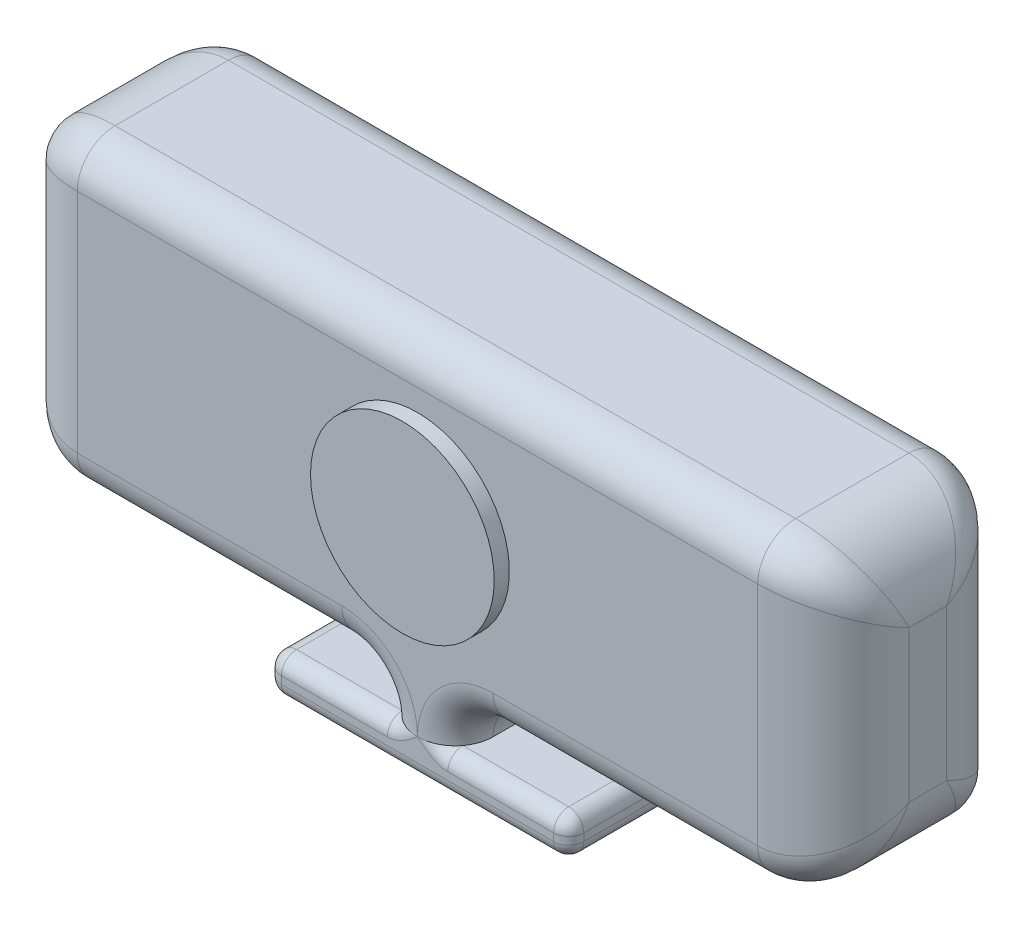
SolidWorks part; units mm, degrees
ref_plane "Front Plane" through (0, 0, 0) normal (0, 0, 1) x (1, 0, 0)
ref_plane "Top Plane" through (0, 0, 0) normal (0, 1, 0) x (1, 0, 0)
ref_plane "Right Plane" through (0, 0, 0) normal (1, 0, 0) x (0, 0, -1)
sketch "Sketch1" plane through (0, 0, 0) normal (0, 0, 1) x (1, 0, 0)
  line L0 (-55, -20) -> (-5, -20)
  line L1 (-55, 20) -> (55, 20)
  line L2 (-55, 20) -> (-55, -20)
  line L4 (55, 20) -> (55, -20)
  line L5 (-55, 20) -> (55, -20) construction
  line L6 (-55, -20) -> (55, 20) construction
  line L7 (-5, -20) -> (-5, -25)
  line L8 (-5, -25) -> (-20, -25)
  line L9 (-20, -25) -> (-20, -30)
  line L10 (-20, -30) -> (20, -30)
  line L11 (20, -30) -> (20, -25)
  line L12 (20, -25) -> (5, -25)
  line L13 (5, -25) -> (5, -20)
  line L14 (5, -20) -> (55, -20)
  point P0 (0, 0)
  dimension "D1" = 110
  dimension "D2" = 40
  dimension "D3" = 10
  dimension "D4" = 5
  dimension "D5" = 40
  dimension "D6" = 5
extrude "Boss-Extrude1" add sketch "Sketch1" against normal blind 25
sketch "Sketch2" plane through (0, 0, 0) normal (0, 0, 1) x (1, 0, 0)
  circle A0 centre (0, 0) radius 12.1512
extrude "Boss-Extrude2" add sketch "Sketch2" along normal blind 2
fillet "Fillet1" radius 10 8 edges at (-55, -20, -12.5) (-55, 0, -25) (-55, 20, -12.5) (-55, 0, 0) (55, 20, -12.5) (55, 0, -25) (55, -20, -12.5) (55, 0, 0)
fillet "Fillet2" radius 5 16 edges at (-52.0711, -17.0711, -22.0711) (-52.0711, -17.0711, -2.9289) (52.0711, -17.0711, -2.9289) (52.0711, -17.0711, -22.0711) (52.0711, 17.0711, -2.9289) (-52.0711, 17.0711, -2.9289) (52.0711, 17.0711, -22.0711) (-52.0711, 17.0711, -22.0711) (-5, -20, -12.5) (-25, -20, -25) (-25, -20, 0) (5, -20, -12.5) (25, -20, 0) (25, -20, -25) (0, 20, 0) (0, 20, -25)
fillet "Fillet3" radius 2 14 edges at (-20, -30, -12.5) (-20, -25, -12.5) (-20, -27.5, -25) (0, -30, -25) (10, -25, -25) (-10, -25, -25) (0, -30, 0) (-20, -27.5, 0) (-10, -25, 0) (10, -25, 0) (20, -25, -12.5) (20, -27.5, -25) (20, -30, -12.5) (20, -27.5, 0)
